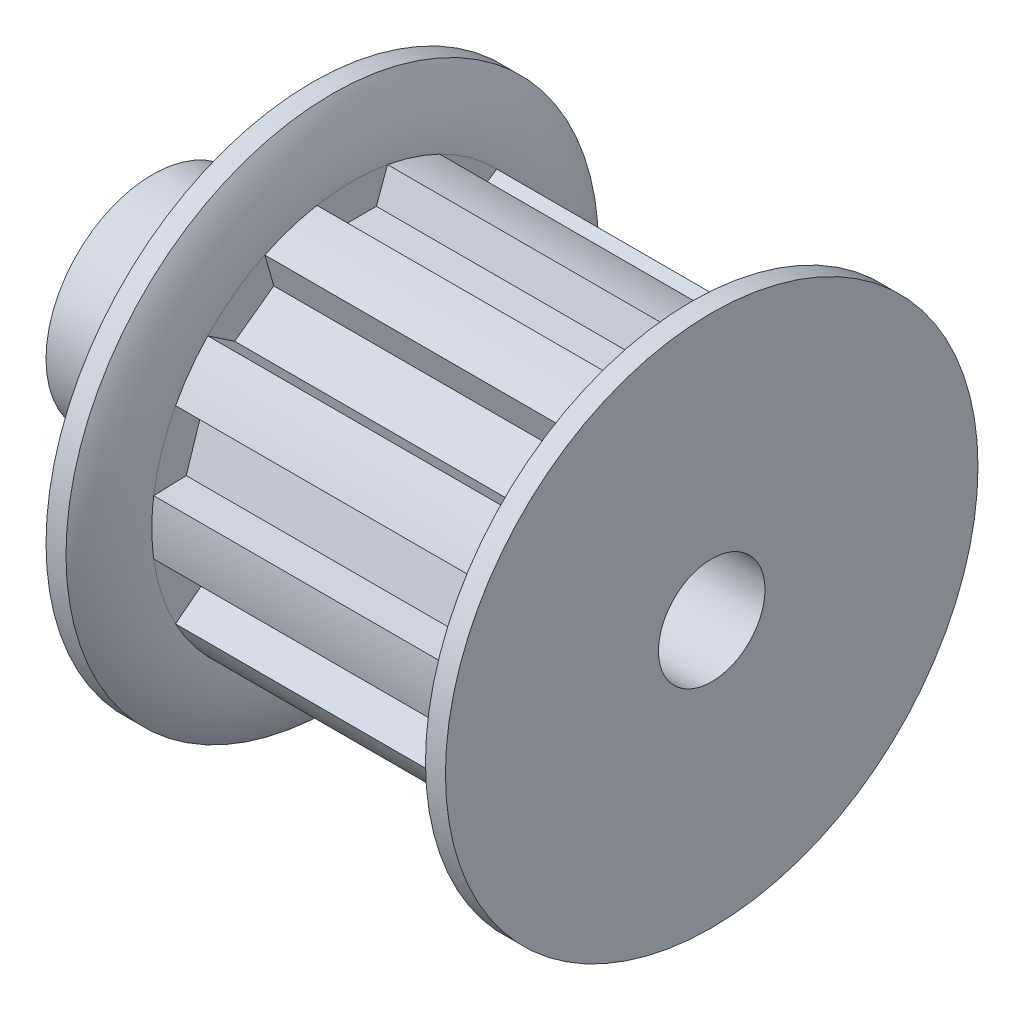
SolidWorks part; units mm, degrees
ref_plane "Front Plane" through (0, 0, 0) normal (0, 0, 1) x (1, 0, 0)
ref_plane "Top Plane" through (0, 0, 0) normal (0, 1, 0) x (1, 0, 0)
ref_plane "Right Plane" through (0, 0, 0) normal (1, 0, 0) x (0, 0, -1)
sketch "Sketch1" plane through (0, 0, 0) normal (1, 0, 0) x (0, 0, -1)
  line L3 (0, 0) -> (0, 6.325) construction
  line L6 (0, 6.325) -> (0, 7.525) construction
  line L7 (-1.325, 7.4074) -> (-0.9072, 6.2596)
  line L8 (1.325, 7.4074) -> (0.9072, 6.2596)
  line L9 (0, -2.2) -> (0, -3.2) construction
  line L10 (0, 8.025) -> (0, 7.525) construction
  line L12 (-0.9072, 6.2596) -> (0.9072, 6.2596)
  line L15 (0, 0) -> (0, -2.2) construction
  circle A0 centre (0, 0) radius 8.025 construction
  circle A1 centre (0, 0) radius 6.325 construction
  arc A7 (1.325, 7.4074) -> (-1.325, 7.4074) centre (0, 0) ccw
  dimension "PD" = 16.05
  dimension "D1" = 40
  dimension "D3" = 0.5
  dimension "D2" = 1.2
  dimension "D4" = 2.65
sketch "Sketch2" plane through (0, 0, 0) normal (0, 0, 1) x (1, 0, 0)
  line L0 (-10.5, 0) -> (10.5, 0) construction
  line L1 (-10.5, 2) -> (10.5, 2)
  line L2 (-10.5, 2) -> (-10.5, 4)
  line L3 (-4.5, 10) -> (-3.75, 10)
  line L4 (-3, 7.525) -> (-4.5, 7.525) construction
  line L5 (9.75, 7.525) -> (9.75, 10) construction
  line L6 (-3, 7.525) -> (9, 7.525)
  line L8 (9, 7.525) -> (10.5, 7.525) construction
  line L9 (9.75, 10) -> (10.5, 10)
  line L10 (10.5, 10) -> (10.5, 2)
  line L12 (-7.5, 4) -> (-7.5, 2) construction
  line L13 (-4.5, 10) -> (-4.5, 4)
  line L14 (-4.5, 4) -> (-10.5, 4)
  arc A0 (9, 7.525) -> (9.75, 10) centre (13.4588, 7.525) cw
  arc A1 (-3, 7.525) -> (-3.75, 10) centre (-7.4588, 7.525) ccw
  point P19 (-3, 7.525)
  point P20 (9, 7.525)
  dimension "Bore Size" = 4
  dimension "Overall Width" = 21
  dimension "Inside Width" = 12
  dimension "Outside Width" = 15
  dimension "Hub Dia" = 8
  dimension "OD" = 20
sketch "Sketch6" plane through (0, 0, 0) normal (0, 0, 1) x (1, 0, 0)
  line L0 (9.75, 10) -> (10.5, 10) construction
  line L1 (-3, 7.525) -> (9, 7.525) construction
  line L2 (-4.5, 10) -> (-3.75, 10) construction
  line L3 (-4.5, 10) -> (-4.5, 4) construction
  line L4 (-4.5, 4) -> (-10.5, 4) construction
  line L5 (-10.5, 2) -> (-10.5, 4) construction
  line L6 (-10.5, 2) -> (10.5, 2) construction
  line L7 (10.5, 10) -> (10.5, 2) construction
  line L8 (9.75, 10) -> (10.5, 10)
  line L9 (-3, 7.525) -> (9, 7.525)
  line L10 (-4.5, 10) -> (-3.75, 10)
  line L11 (-4.5, 10) -> (-4.5, 4)
  line L12 (-4.5, 4) -> (-10.5, 4)
  line L13 (-10.5, 2) -> (-10.5, 4)
  line L14 (-10.5, 2) -> (10.5, 2)
  line L15 (10.5, 10) -> (10.5, 2)
  arc A0 (9.75, 10) -> (9, 7.525) centre (13.4588, 7.525) ccw construction
  arc A1 (-3, 7.525) -> (-3.75, 10) centre (-7.4588, 7.525) ccw construction
  arc A2 (9.75, 10) -> (9, 7.525) centre (13.4588, 7.525) ccw
  arc A3 (-3, 7.525) -> (-3.75, 10) centre (-7.4588, 7.525) ccw
revolve "Revolve1" add sketch "Sketch6" angle 360 about L0
sketch "Sketch3" plane through (0, 0, 0) normal (1, 0, 0) x (0, 0, -1)
  line L2 (-1.325, 7.4074) -> (-0.9072, 6.2596) construction
  line L3 (-0.9072, 6.2596) -> (0.9072, 6.2596) construction
  line L4 (1.325, 7.4074) -> (0.9072, 6.2596) construction
  line L5 (-1.325, 7.4074) -> (-0.9072, 6.2596)
  line L6 (-0.9072, 6.2596) -> (0.9072, 6.2596)
  line L7 (1.325, 7.4074) -> (0.9072, 6.2596)
  arc A1 (1.325, 7.4074) -> (-1.325, 7.4074) centre (0, 0) ccw construction
  arc A2 (1.325, 7.4074) -> (-1.325, 7.4074) centre (0, 0) ccw
extrude "Cut-Extrude1" cut sketch "Sketch3" along normal up to vertex (9 mm away) from vertex up to point (9, 7.525, 0) starting at point (-3, 7.525, 0)
pattern_circular "CirPattern1" count 10 over 360 about axis through (-10.5, 0, 0) along (-1, 0, 0) of "Cut-Extrude1"
sketch "Sketch5" plane through (0, 0, 0) normal (0, 0, 1) x (1, 0, 0)
  line L0 (-10.5, 0) -> (10.5, 0) construction
  point P0 (9, 0)
ref_axis "Center Axis 1" through (10.5, 0, 0) along (-1, 0, 0)
equation "\"D3@Sketch1\" = \"ht@Sketch1\" / 2"
equation "\"D2@Sketch1\" = \"hs@Sketch1\" - \"ht@Sketch1\""
